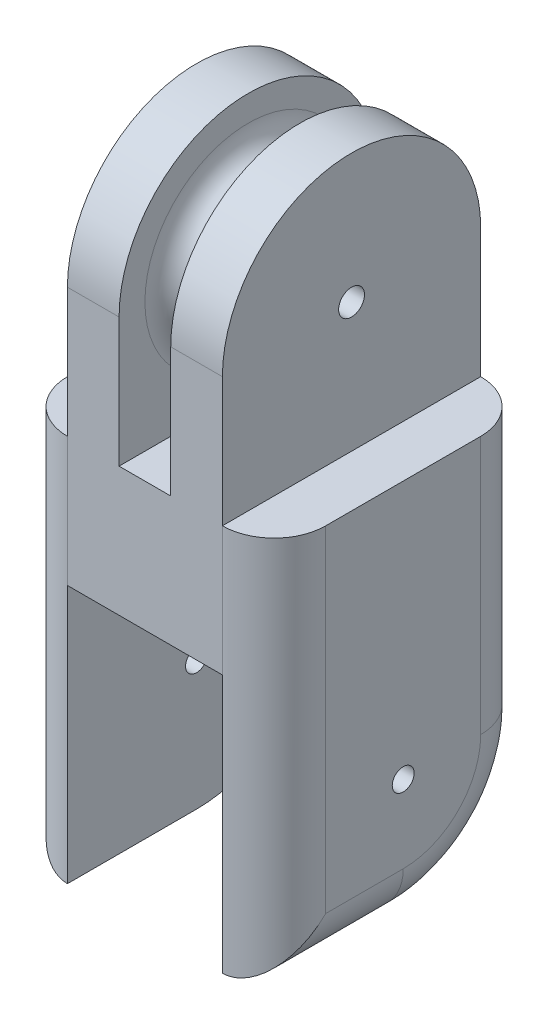
SolidWorks part; units mm, degrees
ref_plane "Front Plane" through (0, 0, 0) normal (0, 0, 1) x (1, 0, 0)
ref_plane "Top Plane" through (0, 0, 0) normal (0, 1, 0) x (1, 0, 0)
ref_plane "Right Plane" through (0, 0, 0) normal (1, 0, 0) x (0, 0, -1)
sketch "Sketch1" plane through (0, 0, 0) normal (0, 1, 0) x (1, 0, 0)
  line L0 (10, 10) -> (-10, -10) construction
  line L1 (-10, 10) -> (10, 10)
  line L2 (-10, 10) -> (-10, -10)
  line L3 (-10, -10) -> (10, -10)
  line L4 (10, 10) -> (10, -10)
  line L5 (-10, 10) -> (10, -10) construction
  point P5 (0, 0)
  dimension "D1" = 20
  dimension "D2" = 20
extrude "Boss-Extrude1" add sketch "Sketch1" along normal blind 10
sketch "Sketch4" plane through (0, 0, 0) normal (0, -1, 0) x (1, 0, 0)
  line L0 (10, -10) -> (-10, -10) construction
  line L1 (-10, 10) -> (-6, 10)
  line L2 (-10, 10) -> (-10, -10)
  line L3 (-10, -10) -> (-6, -10)
  line L4 (-6, 10) -> (-6, -10)
  line L5 (-10, 10) -> (10, 10) construction
  line L6 (10, -10) -> (6, -10)
  line L7 (10, -10) -> (10, 10)
  line L8 (10, 10) -> (6, 10)
  line L9 (6, -10) -> (6, 10)
  dimension "D1" = 4
  dimension "D2" = 4
extrude "Boss-Extrude2" add sketch "Sketch4" along normal blind 10
sketch "Sketch5" plane through (-10, 0, 0) normal (-1, 0, 0) x (0, 0, 1)
  line L0 (10, -10) -> (-10, -10) construction
  line L4 (0, -20) -> (10, -20)
  line L5 (10, -10) -> (10, -20)
  arc A0 (10, -10) -> (0, -20) centre (0, -10) ccw
extrude "Boss-Extrude3" add sketch "Sketch5" against normal blind 4
sketch "Sketch6" plane through (10, 0, 0) normal (1, 0, 0) x (0, 0, -1)
  line L0 (10, -10) -> (-10, -10) construction
  line L4 (0, -20) -> (-10, -20)
  line L5 (-10, -10) -> (-10, -20)
  arc A0 (0, -20) -> (-10, -10) centre (0, -10) ccw
extrude "Boss-Extrude4" add sketch "Sketch6" against normal blind 4
sketch "Sketch7" plane through (-10, 0, 0) normal (-1, 0, 0) x (0, 0, 1)
  circle A0 centre (0, -10) radius 0.85
  dimension "D1" = 1.7
extrude "Cut-Extrude1" cut sketch "Sketch7" against normal through all
fillet "Fillet1" radius 4 8 edges at (-10, -5, 10) (-10, -17.0711, -7.0711) (10, -5, 10) (10, -17.0711, -7.0711) (-10, 0, -10) (10, 0, -10) (10, -20, 5) (-10, -20, 5)
sketch "Sketch8" plane through (0, 10, 0) normal (0, 1, 0) x (1, 0, 0)
  line L0 (6, 10) -> (-6, 10) construction
  line L1 (6, -10) -> (2, -10)
  line L2 (6, -10) -> (6, 10)
  line L3 (6, 10) -> (2, 10)
  line L4 (2, -10) -> (2, 10)
  line L5 (-10, 6) -> (-10, -6) construction
  line L6 (-6, -10) -> (-2, -10)
  line L7 (-6, -10) -> (-6, 10)
  line L8 (-6, 10) -> (-2, 10)
  line L9 (-2, -10) -> (-2, 10)
  line L10 (10, -6) -> (10, 6) construction
  dimension "D1" = 4
  dimension "D2" = 4
  dimension "D3" = 4
  dimension "D4" = 4
extrude "Boss-Extrude5" add sketch "Sketch8" along normal blind 10
sketch "Sketch9" plane through (6, 0, 0) normal (1, 0, 0) x (0, 0, -1)
  line L0 (-10, 20) -> (10, 20) construction
  circle A0 centre (0, 20) radius 10
extrude "Boss-Extrude6" add sketch "Sketch9" against normal blind 4
sketch "Sketch10" plane through (-6, 0, 0) normal (-1, 0, 0) x (0, 0, 1)
  line L0 (-10, 20) -> (10, 20) construction
  circle A0 centre (0, 20) radius 10
extrude "Boss-Extrude7" add sketch "Sketch10" against normal blind 4
sketch "Sketch12" plane through (-6, 0, 0) normal (-1, 0, 0) x (0, 0, 1)
  circle A0 centre (0, 20) radius 1
  dimension "D1" = 2
extrude "Cut-Extrude2" cut sketch "Sketch12" against normal through all
sketch "Sketch13" plane through (-2, 0, 0) normal (1, 0, 0) x (0, 0, -1)
  circle A0 centre (0, 20) radius 6
  dimension "D1" = 12
sketch "Sketch14" plane through (-2, 0, 0) normal (1, 0, 0) x (0, 0, -1)
  circle A0 centre (0, 20) radius 3.5
  dimension "D1" = 7
extrude "Boss-Extrude8" add sketch "Sketch13" along normal blind 4
extrude "Cut-Extrude3" cut sketch "Sketch14" along normal blind 4
fillet "Fillet2" radius 2 2 edges at (2, 20, -6) (-2, 20, 6)
sketch "Sketch16" plane through (0, 0, 0) normal (0, -1, 0) x (1, 0, 0)
  line L0 (6, -10) -> (-6, -10) construction
  line L1 (-6, 0) -> (6, 0) construction
  line L2 (-6, -10) -> (-6, 10) construction
  line L3 (6, 10) -> (6, -10) construction
  circle A0 centre (0, -6) radius 0.5
  circle A1 centre (0, 6) radius 0.5
  dimension "D1" = 1
  dimension "D2" = 4
extrude "Cut-Extrude4" cut sketch "Sketch16" against normal up to next
